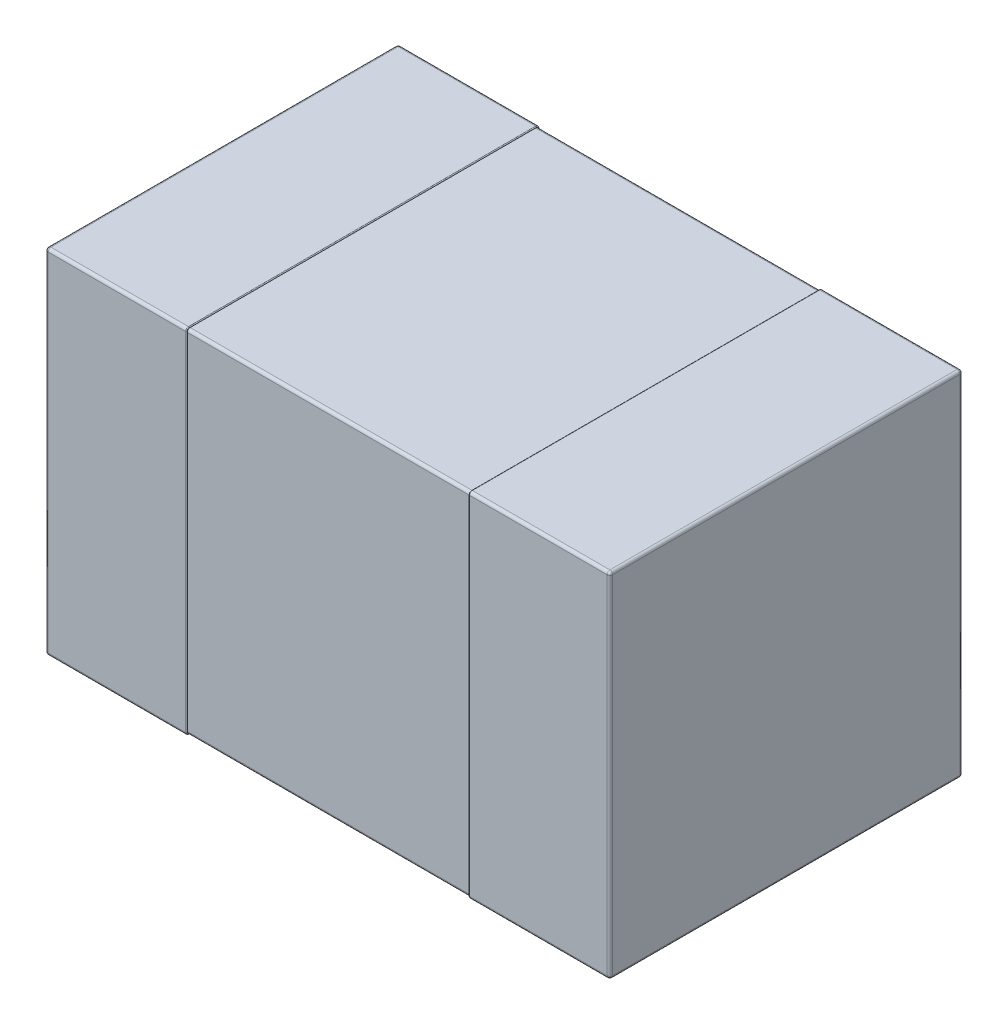
SolidWorks part; units mm, degrees
ref_plane "Top Plane" through (0, 0, 0) normal (0, 0, 1) x (1, 0, 0)
ref_plane "Front Plane" through (0, 0, 0) normal (0, 1, 0) x (1, 0, 0)
ref_plane "Side Plane" through (0, 0, 0) normal (1, 0, 0) x (0, 0, -1)
sketch "Sketch1" plane through (0, 0, 0) normal (0, 0, 1) x (1, 0, 0)
  line L1 (-1, 0.625) -> (1, 0.625)
  line L2 (-1, 0.625) -> (-1, -0.625)
  line L3 (-1, -0.625) -> (1, -0.625)
  line L4 (1, 0.625) -> (1, -0.625)
  dimension "D1" = 2
  dimension "D2" = 1
  dimension "D3" = 1.25
  dimension "D4" = 0.625
extrude "All body" add sketch "Sketch1" along normal blind 1.25
sketch "Sketch2" plane through (0, 0, 0) normal (1, 0, 0) x (0, 0, -1)
  line L14 (-0.003, 0.622) -> (-1.247, 0.622)
  line L15 (-0.003, -0.622) -> (-0.003, 0.622)
  line L16 (-1.247, -0.622) -> (-0.003, -0.622)
  line L17 (-1.247, 0.622) -> (-1.247, -0.622)
  line L18 (-0.003, 0.622) -> (-1.247, 0.622)
  line L19 (-0.003, -0.622) -> (-0.003, 0.622)
  line L20 (-1.247, -0.622) -> (-0.003, -0.622)
  line L21 (-1.247, 0.622) -> (-1.247, -0.622)
  dimension "D1" = 0.003
extrude "Cut out the body for pin" cut sketch "Sketch2" against normal blind 0.5 and the other way blind 0.5 flip side to cut
fillet "Body fillet" radius 0.01 4 edges at (0, 0.622, 0.003) (0, 0.622, 1.247) (0, -0.622, 0.003) (0, -0.622, 1.247)
fillet "Pin fillet a" radius 0.01 16 edges at (1, -0.625, 0.625) (1, 0, 1.25) (1, 0.625, 0.625) (1, 0, 0) (-1, 0.625, 0.625) (-1, 0, 1.25) (-1, -0.625, 0.625) (-1, 0, 0) (0.75, 0.625, 1.25) (0.75, -0.625, 1.25) (0.75, -0.625, 0) (0.75, 0.625, 0) (-0.75, 0.625, 0) (-0.75, -0.625, 0) (-0.75, 0.625, 1.25) (-0.75, -0.625, 1.25)
fillet "Pin fillet b" radius 0.003 16 edges at (0.5, -0.6221, 1.2471) (0.5, -0.625, 0.625) (0.5, -0.6221, 0.0029) (0.5, 0, 0) (0.5, 0.6221, 0.0029) (0.5, 0.625, 0.625) (0.5, 0.6221, 1.2471) (-0.5, -0.6221, 1.2471) (-0.5, -0.625, 0.625) (-0.5, -0.6221, 0.0029) (-0.5, 0, 0) (-0.5, 0.6221, 0.0029) (-0.5, 0.625, 0.625) (-0.5, 0.6221, 1.2471) (0.5, 0, 1.25) (-0.5, 0, 1.25)
